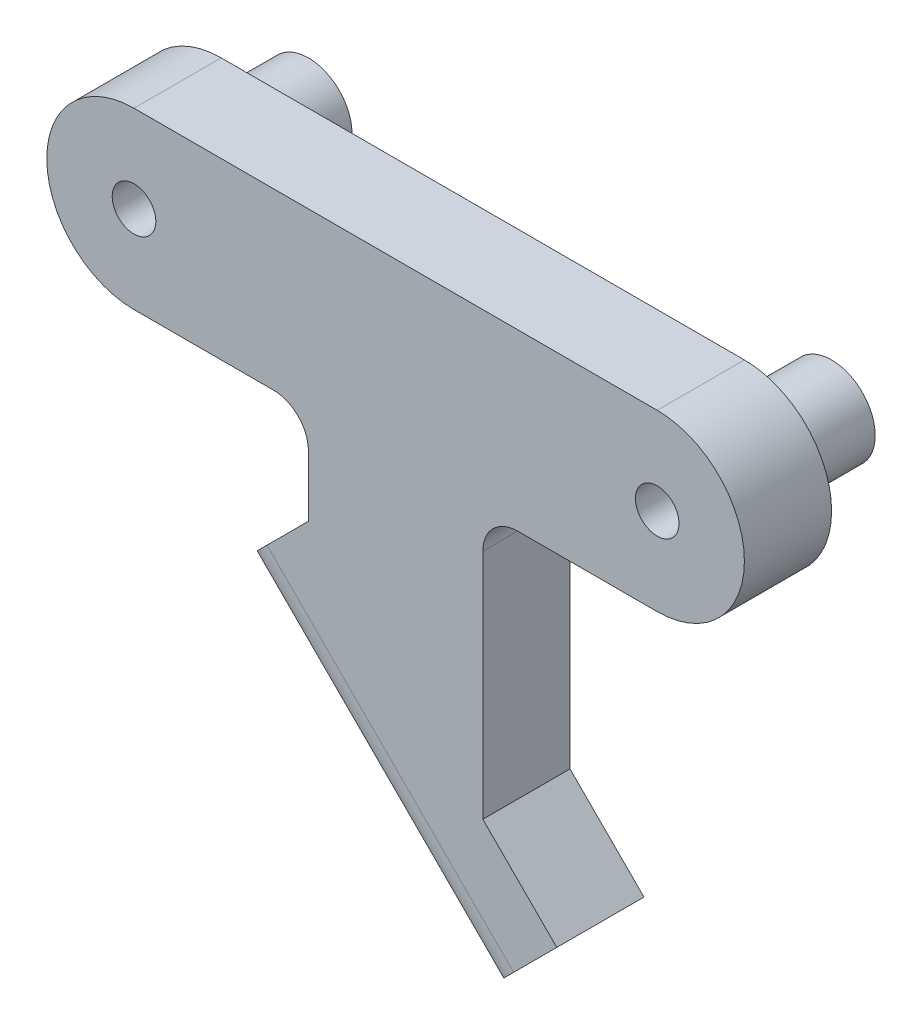
SolidWorks part; units mm, degrees
ref_plane "Piano frontale" through (0, 0, 0) normal (0, 0, 1) x (1, 0, 0)
ref_plane "Piano superiore" through (0, 0, 0) normal (0, 1, 0) x (1, 0, 0)
ref_plane "Piano destro" through (0, 0, 0) normal (1, 0, 0) x (0, 0, -1)
sketch "Schizzo1" plane through (0, 0, 0) normal (0, 0, 1) x (1, 0, 0)
  line L1 (-13.208, 5) -> (16.792, 5)
  line L2 (-13.208, -5) -> (-3.208, -5)
  line L3 (6.792, -28.7941) -> (6.792, -18.7941)
  line L4 (-3.208, -18.7941) -> (6.792, -28.7941)
  line L5 (6.792, -5) -> (16.792, -5)
  line L7 (-3.208, -5) -> (-3.208, -18.7941)
  line L9 (6.792, -5) -> (6.792, -18.7941)
  line L10 (6.792, 0) -> (16.792, 0) construction
  arc A0 (-13.208, 5) -> (-13.208, -5) centre (-13.208, 0) ccw
  arc A1 (16.792, -5) -> (16.792, 5) centre (16.792, 0) ccw
  point P3 (1.792, 0)
  dimension "D1" = 30
  dimension "D2" = 10
  dimension "D3" = 10
  dimension "D4" = 10
extrude "Estrusione-Estrusione3" add sketch "Schizzo1" along normal blind 5 contours L2 L7 L4 L3 L9 L5 A1 L1 A0
sketch "Schizzo3" plane through (0, 0, 0) normal (0, 0, -1) x (-1, 0, 0)
  line L6 (13.208, 5) -> (-16.792, 5)
  line L7 (-16.792, -5) -> (-6.792, -5)
  line L8 (-6.792, -5) -> (-6.792, -28.7941)
  line L9 (-6.792, -28.7941) -> (3.208, -18.7941)
  line L10 (3.208, -18.7941) -> (3.208, -5)
  line L11 (3.208, -5) -> (13.208, -5)
  line L12 (13.208, 5) -> (-16.792, 5) construction
  line L13 (-16.792, -5) -> (-6.792, -5) construction
  line L14 (-6.792, -5) -> (-6.792, -28.7941) construction
  line L15 (-6.792, -28.7941) -> (3.208, -18.7941) construction
  line L16 (3.208, -18.7941) -> (3.208, -5) construction
  line L17 (3.208, -5) -> (13.208, -5) construction
  circle A0 centre (-16.792, 0) radius 2.5
  circle A1 centre (13.208, 0) radius 2.5
  arc A2 (13.208, -5) -> (13.208, 5) centre (13.208, 0) ccw
  arc A3 (-16.792, 5) -> (-16.792, -5) centre (-16.792, 0) ccw
  arc A4 (13.208, -5) -> (13.208, 5) centre (13.208, 0) ccw construction
  arc A5 (-16.792, 5) -> (-16.792, -5) centre (-16.792, 0) ccw construction
  dimension "D1" = 0
extrude "Estrusione-Estrusione4" add sketch "Schizzo3" along normal blind 5
ref_plane "Piano1" through (17.7931, -17.7931, 0) normal (-0.7071, 0.7071, 0) x (0, 0, -1)
sketch "Schizzo7" plane through (17.7931, -17.7931, 0) normal (-0.7071, 0.7071, 0) x (0, 0, -1)
  line L0 (-5, 15.5578) -> (-5, -1.2671) construction
  line L1 (0, 15.5578) -> (-5, 15.5578)
  line L2 (0, 15.5578) -> (0, 9.5578)
  line L3 (0, 9.5578) -> (-5, 9.5578)
  line L4 (-5, 15.5578) -> (-5, 9.5578)
  dimension "D1" = 6
extrude "Estrusione-Estrusione5" add sketch "Schizzo7" along normal blind 20
sketch "Schizzo6" plane through (17.7931, -17.7931, 0) normal (-0.7071, 0.7071, 0) x (0, 0, -1)
  line L0 (0, -1.2671) -> (0, 9.5578) construction
  line L1 (-5, 15.5578) -> (0, 15.5578) construction
  circle A0 centre (-2.5, 12.5578) radius 1.65
  dimension "D1" = 3.3
  dimension "D2" = 2.5
  dimension "D3" = 3
extrude "Taglio-Estrusione1" cut sketch "Schizzo6" along normal up to surface (20 mm away) up to face at (-5.2791, -12.5809, 2.5)
fillet "Raccordo1" radius 2.5 2 edges at (-0.2791, -21.723, 0) (-0.2791, -21.723, 5)
sketch "Schizzo8" plane through (0, 0, -5) normal (0, 0, -1) x (-1, 0, 0)
  circle A0 centre (-16.792, 0) radius 1.25
  circle A1 centre (13.208, 0) radius 1.25
  dimension "D1" = 2.5
extrude "Taglio-Estrusione2" cut sketch "Schizzo8" against normal through all
fillet "Raccordo2" radius 2 2 edges at (-3.208, -5, 2.5) (6.792, -5, 2.5)
